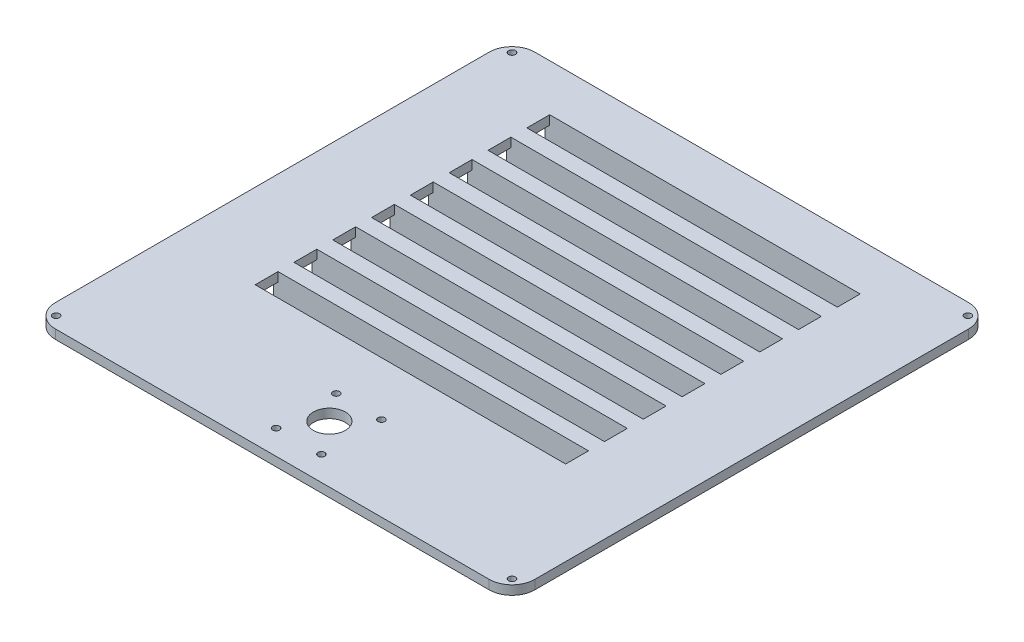
SolidWorks part; units mm, degrees
ref_plane "Front Plane" through (0, 0, 0) normal (0, 0, 1) x (1, 0, 0)
ref_plane "Top Plane" through (0, 0, 0) normal (0, 1, 0) x (1, 0, 0)
ref_plane "Right Plane" through (0, 0, 0) normal (1, 0, 0) x (0, 0, -1)
sketch "Sketch1" plane through (0, 0, 0) normal (0, 1, 0) x (1, 0, 0)
  line L0 (-101, -101) -> (-101, 101)
  line L5 (-105, -105) -> (105, -105)
  line L6 (-105, -105) -> (-105, 105)
  line L7 (-105, 105) -> (105, 105)
  line L8 (105, -105) -> (105, 105)
  line L9 (-101, 101) -> (101, 101)
  line L10 (101, -101) -> (101, 101)
  line L11 (-101, -101) -> (101, -101)
  line L12 (-101, 101) -> (-99.8333, 99.8333) construction
  line L13 (-55, 0) -> (55, 0) construction
  line L14 (-101, -101) -> (-99.8333, -99.8333) construction
  line L15 (0, -55) -> (0, 55) construction
  line L16 (101, -101) -> (99.8333, -99.8333) construction
  line L17 (101, 101) -> (99.8333, 99.8333) construction
  circle A1 centre (-99.8333, 99.8333) radius 1.5
  circle A2 centre (-99.8333, -99.8333) radius 1.5
  circle A3 centre (99.8333, -99.8333) radius 1.5
  circle A4 centre (99.8333, 99.8333) radius 1.5
  point P0 (0, 0)
  point P6 (-105, 0)
  point P7 (0, 105)
  dimension "D3" = 4
  dimension "D4" = 3
  dimension "D1" = 210
  dimension "D2" = 210
  dimension "D5" = 1.65
  dimension "D6" = 45
extrude "MainExtrude" add sketch "Sketch1" along normal blind 4 contours L6 L5 L8 L7
extrude "ScrewHoles" cut sketch "Sketch1<6>" along normal up to surface (4 mm away) contours A1 | A2 | A3 | A4 up to face at (0, 4, 0)
sketch "Sketch1<6>" plane through (0, 0, 0) normal (0, 1, 0) x (1, 0, 0) same geometry as "Sketch1"
fillet "RoundedCorners" radius 10 4 edges at (-105, 2, -105) (-105, 2, 105) (105, 2, -105) (105, 2, 105)
sketch "Sketch3" plane through (0, 0, 0) normal (0, 1, 0) x (1, 0, 0)
  line L145 (-68, 96.5) -> (68, 96.5) construction
  line L146 (-68, 96.5) -> (-68, -56.5) construction
  line L147 (-68, -56.5) -> (68, -56.5) construction
  line L148 (68, 96.5) -> (68, -56.5) construction
  line L149 (-68, 96.5) -> (68, -56.5) construction
  line L151 (68, 96.5) -> (-68, -56.5) construction
  line L152 (-68, 79.5) -> (68, 79.5) construction
  line L154 (-68, 62.5) -> (68, 62.5) construction
  line L155 (-68, 45.5) -> (68, 45.5) construction
  line L157 (-68, 28.5) -> (68, 28.5) construction
  line L158 (-68, 11.5) -> (68, 11.5) construction
  line L159 (-68, -5.5) -> (68, -5.5) construction
  line L160 (-68, -22.5) -> (68, -22.5) construction
  line L161 (-68, -39.5) -> (68, -39.5) construction
  line L162 (-68, 74.5) -> (68, 74.5)
  line L163 (-68, 57.5) -> (68, 57.5)
  line L164 (-68, 40.5) -> (68, 40.5)
  line L165 (-68, 23.5) -> (68, 23.5)
  line L166 (-68, 6.5) -> (68, 6.5)
  line L167 (-68, -10.5) -> (68, -10.5)
  line L168 (-68, -27.5) -> (68, -27.5)
  line L169 (-68, -44.5) -> (68, -44.5)
  line L170 (-68, 84.5) -> (68, 84.5)
  line L171 (-68, 67.5) -> (68, 67.5)
  line L172 (-68, 50.5) -> (68, 50.5)
  line L173 (-68, 33.5) -> (68, 33.5)
  line L174 (-68, 16.5) -> (68, 16.5)
  line L175 (-68, -0.5) -> (68, -0.5)
  line L176 (-68, -17.5) -> (68, -17.5)
  line L177 (-68, -34.5) -> (68, -34.5)
  line L178 (-68, 74.5) -> (-68, 84.5)
  line L179 (68, 74.5) -> (68, 84.5)
  line L180 (-68, 57.5) -> (-68, 67.5)
  line L181 (68, 57.5) -> (68, 67.5)
  line L182 (-68, 40.5) -> (-68, 50.5)
  line L183 (68, 40.5) -> (68, 50.5)
  line L184 (-68, 23.5) -> (-68, 33.5)
  line L185 (68, 23.5) -> (68, 33.5)
  line L186 (-68, 6.5) -> (-68, 16.5)
  line L187 (68, 6.5) -> (68, 16.5)
  line L188 (-68, -10.5) -> (-68, -0.5)
  line L189 (68, -10.5) -> (68, -0.5)
  line L190 (-68, -27.5) -> (-68, -17.5)
  line L191 (68, -27.5) -> (68, -17.5)
  line L192 (-68, -44.5) -> (-68, -34.5)
  line L193 (68, -44.5) -> (68, -34.5)
  line L200 (-9, -68) -> (-9, -94.3) construction
  line L201 (-95, -105) -> (95, -105) construction
  line L207 (-97.2358, 20) -> (95.5763, 20) construction
  line L208 (-9, -68) -> (10.8, -68) construction
  circle A0 centre (0, -80) radius 7
  circle A1 centre (-9, -68) radius 1.5
  circle A2 centre (-9, -94.3) radius 1.5
  circle A3 centre (10.8, -94.3) radius 1.5
  circle A4 centre (10.8, -68) radius 1.5
  point P70 (0, 20)
  dimension "D18" = 14
  dimension "D19" = 25
  dimension "D21" = 35.5
  dimension "D25" = 3
  dimension "D26" = 3
  dimension "D27" = 19.8
  dimension "D15" = 9
  dimension "D16" = 12
  dimension "D1" = 136
  dimension "D2" = 153
  dimension "D3" = 17
  dimension "D4" = 17
  dimension "D5" = 17
  dimension "D6" = 17
  dimension "D7" = 17
  dimension "D8" = 17
  dimension "D9" = 17
  dimension "D11" = 17
  dimension "D13" = 5
  dimension "D14" = 129
  dimension "D10" = 17
  dimension "D12" = 5
  dimension "D17" = 10.8
  dimension "D20" = 20
  dimension "D22" = 14.3
  dimension "D28" = 26.3
extrude "Trench" cut sketch "Sketch3" along normal blind 10
sketch "Sketch4" plane through (0, 0, 0) normal (0, 1, 0) x (1, 0, 0)
  line L0 (68, -34.5) -> (68, -44.5) construction
  line L1 (68, -44.5) -> (-68, -44.5) construction
  line L2 (-68, -44.5) -> (-68, -34.5) construction
  line L3 (-68, -34.5) -> (68, -34.5) construction
  line L4 (68, -17.5) -> (68, -27.5) construction
  line L5 (68, -27.5) -> (-68, -27.5) construction
  line L6 (-68, -27.5) -> (-68, -17.5) construction
  line L7 (-68, -17.5) -> (68, -17.5) construction
  line L8 (68, -0.5) -> (68, -10.5) construction
  line L9 (68, -10.5) -> (-68, -10.5) construction
  line L10 (-68, -10.5) -> (-68, -0.5) construction
  line L11 (-68, -0.5) -> (68, -0.5) construction
  line L12 (68, 16.5) -> (68, 6.5) construction
  line L13 (68, 6.5) -> (-68, 6.5) construction
  line L14 (-68, 6.5) -> (-68, 16.5) construction
  line L15 (-68, 16.5) -> (68, 16.5) construction
  line L16 (68, 33.5) -> (68, 23.5) construction
  line L17 (68, 23.5) -> (-68, 23.5) construction
  line L18 (-68, 23.5) -> (-68, 33.5) construction
  line L19 (-68, 33.5) -> (68, 33.5) construction
  line L20 (68, 50.5) -> (68, 40.5) construction
  line L21 (68, 40.5) -> (-68, 40.5) construction
  line L22 (-68, 40.5) -> (-68, 50.5) construction
  line L23 (-68, 50.5) -> (68, 50.5) construction
  line L24 (68, 67.5) -> (68, 57.5) construction
  line L25 (68, 57.5) -> (-68, 57.5) construction
  line L26 (-68, 57.5) -> (-68, 67.5) construction
  line L27 (-68, 67.5) -> (68, 67.5) construction
  line L28 (68, 84.5) -> (68, 74.5) construction
  line L29 (68, 74.5) -> (-68, 74.5) construction
  line L30 (-68, 74.5) -> (-68, 84.5) construction
  line L31 (-68, 84.5) -> (68, 84.5) construction
  line L32 (68, -34.5) -> (68, -44.5)
  line L33 (68, -44.5) -> (-68, -44.5)
  line L34 (-68, -44.5) -> (-68, -34.5)
  line L35 (-68, -34.5) -> (68, -34.5)
  line L36 (68, -17.5) -> (68, -27.5)
  line L37 (68, -27.5) -> (-68, -27.5)
  line L38 (-68, -27.5) -> (-68, -17.5)
  line L39 (-68, -17.5) -> (68, -17.5)
  line L40 (68, -0.5) -> (68, -10.5)
  line L41 (68, -10.5) -> (-68, -10.5)
  line L42 (-68, -10.5) -> (-68, -0.5)
  line L43 (-68, -0.5) -> (68, -0.5)
  line L44 (68, 16.5) -> (68, 6.5)
  line L45 (68, 6.5) -> (-68, 6.5)
  line L46 (-68, 6.5) -> (-68, 16.5)
  line L47 (-68, 16.5) -> (68, 16.5)
  line L48 (68, 33.5) -> (68, 23.5)
  line L49 (68, 23.5) -> (-68, 23.5)
  line L50 (-68, 23.5) -> (-68, 33.5)
  line L51 (-68, 33.5) -> (68, 33.5)
  line L52 (68, 50.5) -> (68, 40.5)
  line L53 (68, 40.5) -> (-68, 40.5)
  line L54 (-68, 40.5) -> (-68, 50.5)
  line L55 (-68, 50.5) -> (68, 50.5)
  line L56 (68, 67.5) -> (68, 57.5)
  line L57 (68, 57.5) -> (-68, 57.5)
  line L58 (-68, 57.5) -> (-68, 67.5)
  line L59 (-68, 67.5) -> (68, 67.5)
  line L60 (68, 84.5) -> (68, 74.5)
  line L61 (68, 74.5) -> (-68, 74.5)
  line L62 (-68, 74.5) -> (-68, 84.5)
  line L63 (-68, 84.5) -> (68, 84.5)
  line L64 (70, 86.5) -> (70, 72.5)
  line L65 (70, 72.5) -> (-70, 72.5)
  line L66 (-70, 72.5) -> (-70, 86.5)
  line L67 (-70, 86.5) -> (70, 86.5)
  line L68 (70, 69.5) -> (70, 55.5)
  line L69 (70, 55.5) -> (-70, 55.5)
  line L70 (-70, 55.5) -> (-70, 69.5)
  line L71 (-70, 69.5) -> (70, 69.5)
  line L72 (70, 52.5) -> (70, 38.5)
  line L73 (70, 38.5) -> (-70, 38.5)
  line L74 (-70, 38.5) -> (-70, 52.5)
  line L75 (-70, 52.5) -> (70, 52.5)
  line L76 (70, 35.5) -> (70, 21.5)
  line L77 (70, 21.5) -> (-70, 21.5)
  line L78 (-70, 21.5) -> (-70, 35.5)
  line L79 (-70, 35.5) -> (70, 35.5)
  line L80 (70, 18.5) -> (70, 4.5)
  line L81 (70, 4.5) -> (-70, 4.5)
  line L82 (-70, 4.5) -> (-70, 18.5)
  line L83 (-70, 18.5) -> (70, 18.5)
  line L84 (70, 1.5) -> (70, -12.5)
  line L85 (70, -12.5) -> (-70, -12.5)
  line L86 (-70, -12.5) -> (-70, 1.5)
  line L87 (-70, 1.5) -> (70, 1.5)
  line L88 (70, -15.5) -> (70, -29.5)
  line L89 (70, -29.5) -> (-70, -29.5)
  line L90 (-70, -29.5) -> (-70, -15.5)
  line L91 (-70, -15.5) -> (70, -15.5)
  line L92 (70, -32.5) -> (70, -46.5)
  line L93 (70, -46.5) -> (-70, -46.5)
  line L94 (-70, -46.5) -> (-70, -32.5)
  line L95 (-70, -32.5) -> (70, -32.5)
  dimension "D1" = 2
extrude "Trench Walls" add sketch "Sketch4" against normal blind 4
sketch "Sketch5" plane through (0, -4, 0) normal (0, -1, 0) x (1, 0, 0)
  line L0 (-70, -86.5) -> (70, -86.5) construction
  line L1 (70, -86.5) -> (70, -72.5) construction
  line L2 (70, -72.5) -> (-70, -72.5) construction
  line L3 (-70, -72.5) -> (-70, -86.5) construction
  line L4 (-70, -69.5) -> (70, -69.5) construction
  line L5 (70, -69.5) -> (70, -55.5) construction
  line L6 (70, -55.5) -> (-70, -55.5) construction
  line L7 (-70, -55.5) -> (-70, -69.5) construction
  line L8 (-70, -52.5) -> (70, -52.5) construction
  line L9 (70, -52.5) -> (70, -38.5) construction
  line L10 (70, -38.5) -> (-70, -38.5) construction
  line L11 (-70, -38.5) -> (-70, -52.5) construction
  line L12 (-70, -35.5) -> (70, -35.5) construction
  line L13 (70, -35.5) -> (70, -21.5) construction
  line L14 (70, -21.5) -> (-70, -21.5) construction
  line L15 (-70, -21.5) -> (-70, -35.5) construction
  line L16 (-70, -18.5) -> (70, -18.5) construction
  line L17 (70, -18.5) -> (70, -4.5) construction
  line L18 (70, -4.5) -> (-70, -4.5) construction
  line L19 (-70, -4.5) -> (-70, -18.5) construction
  line L20 (-70, -1.5) -> (70, -1.5) construction
  line L21 (70, -1.5) -> (70, 12.5) construction
  line L22 (70, 12.5) -> (-70, 12.5) construction
  line L23 (-70, 12.5) -> (-70, -1.5) construction
  line L24 (-70, 15.5) -> (70, 15.5) construction
  line L25 (70, 15.5) -> (70, 29.5) construction
  line L26 (70, 29.5) -> (-70, 29.5) construction
  line L27 (-70, 29.5) -> (-70, 15.5) construction
  line L28 (-70, 32.5) -> (70, 32.5) construction
  line L29 (70, 32.5) -> (70, 46.5) construction
  line L30 (70, 46.5) -> (-70, 46.5) construction
  line L31 (-70, 46.5) -> (-70, 32.5) construction
  line L32 (-70, -86.5) -> (70, -86.5)
  line L33 (70, -86.5) -> (70, -72.5)
  line L34 (70, -72.5) -> (-70, -72.5)
  line L35 (-70, -72.5) -> (-70, -86.5)
  line L36 (-70, -69.5) -> (70, -69.5)
  line L37 (70, -69.5) -> (70, -55.5)
  line L38 (70, -55.5) -> (-70, -55.5)
  line L39 (-70, -55.5) -> (-70, -69.5)
  line L40 (-70, -52.5) -> (70, -52.5)
  line L41 (70, -52.5) -> (70, -38.5)
  line L42 (70, -38.5) -> (-70, -38.5)
  line L43 (-70, -38.5) -> (-70, -52.5)
  line L44 (-70, -35.5) -> (70, -35.5)
  line L45 (70, -35.5) -> (70, -21.5)
  line L46 (70, -21.5) -> (-70, -21.5)
  line L47 (-70, -21.5) -> (-70, -35.5)
  line L48 (-70, -18.5) -> (70, -18.5)
  line L49 (70, -18.5) -> (70, -4.5)
  line L50 (70, -4.5) -> (-70, -4.5)
  line L51 (-70, -4.5) -> (-70, -18.5)
  line L52 (-70, -1.5) -> (70, -1.5)
  line L53 (70, -1.5) -> (70, 12.5)
  line L54 (70, 12.5) -> (-70, 12.5)
  line L55 (-70, 12.5) -> (-70, -1.5)
  line L56 (-70, 15.5) -> (70, 15.5)
  line L57 (70, 15.5) -> (70, 29.5)
  line L58 (70, 29.5) -> (-70, 29.5)
  line L59 (-70, 29.5) -> (-70, 15.5)
  line L60 (-70, 32.5) -> (70, 32.5)
  line L61 (70, 32.5) -> (70, 46.5)
  line L62 (70, 46.5) -> (-70, 46.5)
  line L63 (-70, 46.5) -> (-70, 32.5)
extrude "Trench Bottom" add sketch "Sketch5" along normal blind 2
sketch "Sketch7" plane through (70, 0, 0) normal (1, 0, 0) x (0, 0, -1)
  line L1 (-44.5, 0) -> (-34.5, 0)
  line L2 (-44.5, 0) -> (-44.5, -6)
  line L3 (-44.5, -6) -> (-34.5, -6)
  line L4 (-34.5, 0) -> (-34.5, -6)
  line L5 (-46.5, -6) -> (-46.5, 0) construction
  line L6 (-32.5, -6) -> (-46.5, -6) construction
  line L7 (-27.5, 0) -> (-27.5, -6)
  line L8 (-27.5, 0) -> (-17.5, 0)
  line L9 (-17.5, 0) -> (-17.5, -6)
  line L10 (-27.5, -6) -> (-17.5, -6)
  line L11 (-10.5, 0) -> (-10.5, -6)
  line L12 (-10.5, 0) -> (-0.5, 0)
  line L13 (-0.5, 0) -> (-0.5, -6)
  line L14 (-10.5, -6) -> (-0.5, -6)
  line L15 (6.5, 0) -> (6.5, -6)
  line L16 (6.5, 0) -> (16.5, 0)
  line L17 (16.5, 0) -> (16.5, -6)
  line L18 (6.5, -6) -> (16.5, -6)
  line L19 (23.5, 0) -> (23.5, -6)
  line L20 (23.5, 0) -> (33.5, 0)
  line L21 (33.5, 0) -> (33.5, -6)
  line L22 (23.5, -6) -> (33.5, -6)
  line L23 (40.5, 0) -> (40.5, -6)
  line L24 (40.5, 0) -> (50.5, 0)
  line L25 (50.5, 0) -> (50.5, -6)
  line L26 (40.5, -6) -> (50.5, -6)
  line L27 (57.5, 0) -> (57.5, -6)
  line L28 (57.5, 0) -> (67.5, 0)
  line L29 (67.5, 0) -> (67.5, -6)
  line L30 (57.5, -6) -> (67.5, -6)
  line L31 (74.5, 0) -> (74.5, -6)
  line L32 (74.5, 0) -> (84.5, 0)
  line L33 (84.5, 0) -> (84.5, -6)
  line L34 (74.5, -6) -> (84.5, -6)
  line L35 (-29.5, -6) -> (-29.5, 0) construction
  line L36 (-46.5, 0) -> (-32.5, 0) construction
  dimension "D3" = 10
  dimension "D4" = 2
  dimension "D5" = 8
  dimension "D6" = 2
extrude "Wire Opening" cut sketch "Sketch7" against normal through all both and the other way through all
sketch "Sketch9" plane through (0, 0, 0) normal (0, -1, 0) x (1, 0, 0)
  line L0 (-95, 105) -> (95, 105) construction
  line L1 (-70, 46.5) -> (70, 46.5) construction
  line L5 (-105, 95) -> (-105, -95) construction
  circle A0 centre (-94, 92) radius 0.98
  circle A1 centre (-94, 92) radius 2
  circle A2 centre (-19.73, 92) radius 2
  circle A3 centre (-19.73, 92) radius 0.98
  circle A4 centre (-94, 56.16) radius 2
  circle A5 centre (-94, 56.16) radius 0.98
  circle A6 centre (-19.73, 56.16) radius 0.98
  circle A7 centre (-19.73, 56.16) radius 2
  circle A8 centre (-99.8333, 99.8333) radius 1.5 construction
  dimension "D1" = 13
  dimension "D2" = 35.84
  dimension "D5" = 1.96
  dimension "D6" = 4
  dimension "D7" = 1.96
  dimension "D8" = 4
  dimension "D3" = 11
  dimension "D4" = 74.27
  dimension "D9" = 9.7666
  dimension "D10" = 9.66
extrude "PCB Holes" add sketch "Sketch9" along normal blind 4
fillet "PCB Rounds" radius 2 4 edges at (-19.73, 0, 58.16) (-19.73, 0, 94) (-94, 0, 58.16) (-94, 0, 94)
equation "\"1_LED\"= 17mm"
equation "\"2_LED\"= \"1_LED\" * 2"
equation "\"3_LED\"= \"1_LED\" * 3"
equation "\"4_LED\"= \"1_LED\" * 4"
equation "\"5_LED\"= \"1_LED\" * 5"
equation "\"6_LED\"= \"1_LED\" * 6"
equation "\"7_LED\"= \"1_LED\" * 7"
equation "\"8_LED\"= \"1_LED\" * 8"
equation "\"9_LED\"= \"1_LED\" * 9"
equation "\"10_LED\"= \"1_LED\" * 10"
equation "\"11_LED\"= \"1_LED\" * 11"
equation "\"12_LED\"= \"1_LED\" * 12"
